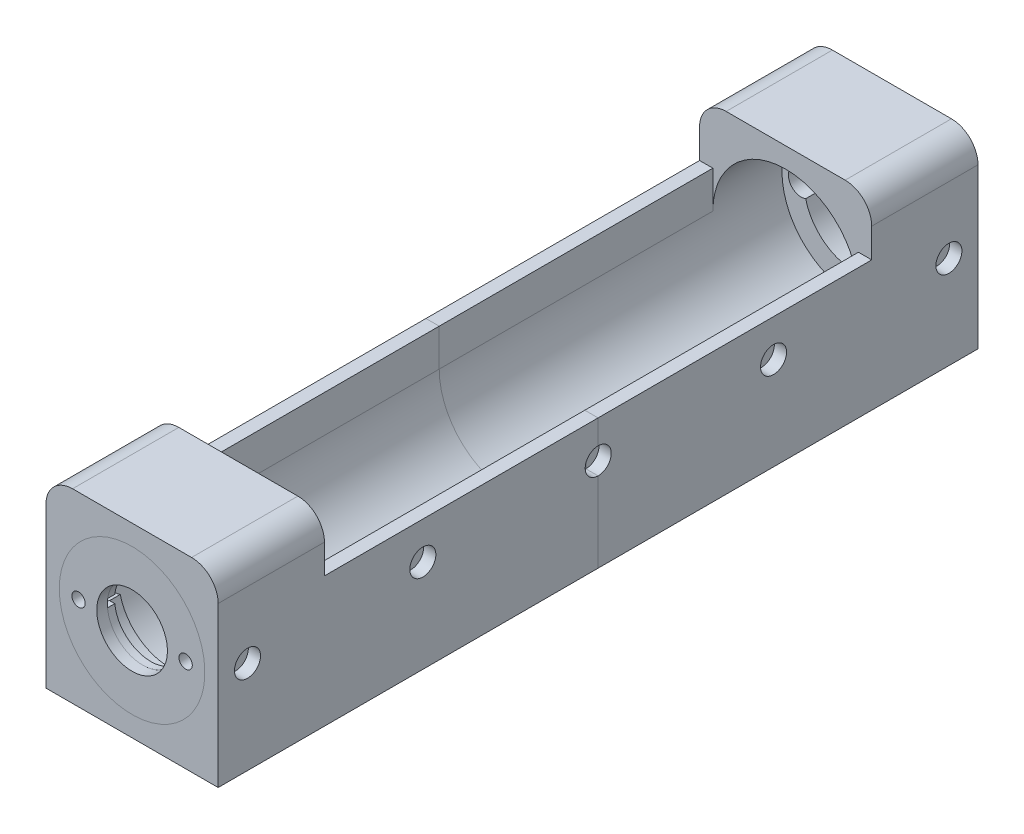
SolidWorks part; units mm, degrees
ref_plane "Alzado" through (0, 0, 0) normal (0, 0, 1) x (1, 0, 0)
ref_plane "Planta" through (0, 0, 0) normal (0, 1, 0) x (1, 0, 0)
ref_plane "Vista lateral" through (0, 0, 0) normal (1, 0, 0) x (0, 0, -1)
sketch "Croquis1" plane through (0, 0, 0) normal (0, 0, 1) x (1, 0, 0)
  line L0 (0, 8.3596) -> (0, -1.3417) construction
  line L1 (9, 0.75) -> (-9, 0.75)
  line L2 (0, 0.75) -> (0, -0.75)
  line L3 (9, -0.75) -> (-9, -0.75)
  line L4 (-9, 0.75) -> (-9, -0.75)
  line L5 (-12.48, 10.7299) -> (-12.48, -4.9079) construction
  line L6 (9, 0.75) -> (9, -0.75)
  line L7 (0, 0) -> (-17.6562, 0) construction
  circle A0 centre (-10.08, 0) radius 2.4
  circle A1 centre (-10.08, 0) radius 0.9
  circle A2 centre (10.08, 0) radius 0.9
  circle A3 centre (10.08, 0) radius 2.4
  circle A4 centre (0, 0) radius 13.7
  point P9 (0, 0)
  dimension "D1" = 1.8
  dimension "D4" = 4.8
  dimension "D6" = 27.4
  dimension "D2" = 1.5
  dimension "D3" = 9
  dimension "D5" = 12.48
extrude "Saliente-Extruir1" add sketch "Croquis1" along normal blind 5 contours A4 L1 A3 L3 A0 region at (-13.3125, 0, 0)
sketch "Croquis2" plane through (0, 0, 5) normal (0, 0, 1) x (1, 0, 0)
  circle A0 centre (0, 0) radius 9.5
  dimension "D1" = 19
extrude "Cortar-Extruir1" cut sketch "Croquis2" against normal blind 3.5
sketch "Croquis3" plane through (0, 0, 1.5) normal (0, 0, 1) x (1, 0, 0)
  circle A0 centre (0, 0) radius 6.8
  dimension "D1" = 13.6
extrude "Cortar-Extruir2" cut sketch "Croquis3" against normal blind 3
sketch "Croquis4" plane through (0, 0, 0) normal (0, 0, -1) x (-1, 0, 0)
  circle A0 centre (0, 0) radius 13.7 construction
  circle A1 centre (0, 0) radius 13.7
  circle A2 centre (0, 0) radius 6.65
  dimension "D1" = 13.3
extrude "Saliente-Extruir2" add sketch "Croquis4" along normal blind 2
sketch "Croquis5" plane through (0, 0, 5) normal (0, 0, 1) x (1, 0, 0)
  circle A0 centre (-10.08, 0) radius 1.25
  circle A1 centre (10.08, 0) radius 1.25
  dimension "D1" = 2.5
  dimension "D2" = 2.5
extrude "Cortar-Extruir3" cut sketch "Croquis5" against normal through all
sketch "Croquis6" plane through (0, 0, -2) normal (0, 0, -1) x (-1, 0, 0)
  line L1 (-16.2, -17.5) -> (16.2, -17.5)
  line L2 (-16.2, -17.5) -> (-16.2, 17.5)
  line L3 (-16.2, 17.5) -> (16.2, 17.5)
  line L4 (16.2, -17.5) -> (16.2, 17.5)
  line L5 (-16.2, -17.5) -> (16.2, 17.5) construction
  line L6 (-16.2, 17.5) -> (16.2, -17.5) construction
  circle A0 centre (0, 0) radius 13.7 construction
  circle A1 centre (0, 0) radius 13.7
  point P0 (0, 0)
  dimension "D1" = 35
  dimension "D2" = 32.4
extrude "Saliente-Extruir3" add sketch "Croquis6" against normal blind 20 separate body
sketch "Croquis8" plane through (0, 0, 18) normal (0, 0, 1) x (1, 0, 0)
  line L0 (-13.7, 0) -> (-13.7, 7)
  line L1 (-13.7, 7) -> (16.2, 7)
  line L2 (13.7, 0) -> (13.7, 7)
  line L3 (13.7, 7) -> (-16.2, 7)
  line L4 (-16.2, 17.5) -> (-16.2, -17.5)
  line L5 (16.2, 17.5) -> (-16.2, 17.5)
  line L6 (16.2, -17.5) -> (16.2, 17.5)
  line L7 (-16.2, -17.5) -> (16.2, -17.5)
  line L8 (-16.2, 17.5) -> (-16.2, 7)
  line L10 (16.2, 7) -> (16.2, 17.5)
  line L11 (-16.2, -17.5) -> (16.2, -17.5)
  line L12 (16.2, 17.5) -> (16.2, -17.5) construction
  line L13 (27.021, 0) -> (-27.7174, 0) construction
  circle A0 centre (0, 0) radius 13.7 construction
  circle A1 centre (0, 0) radius 13.7 construction
  arc A2 (-13.7, 0) -> (13.7, 0) centre (0, 0) ccw
  circle M15 centre (0, 0) radius 13.7
  line M16 (-16.2, 17.5) -> (-16.2, -17.5)
  line M17 (-16.2, -17.5) -> (16.2, -17.5)
  line M18 (16.2, -17.5) -> (16.2, 17.5)
  dimension "D2" = 7
  dimension "D3" = 7
  dimension "D1" = 0
extrude "Saliente-Extruir5" add sketch "Croquis8" along normal blind 51.5 contours L13 M18 M15 M16 M17 | L13 L0 L3 M16 | L13 L1 L2 M18 region at (-14.95, 3.5, 18) region at (0, -14.0682, 18) region at (14.95, 3.5, 18)
ref_plane "Plano1" through (0, 0, 69.5) normal (0, 0, 1) x (1, 0, 0)
mirror "Simetría10" about plane through (0, 0, 69.5) normal (0, 0, 1) of bodies 105 108
sketch "Croquis9" plane through (-16.2, 0, 0) normal (-1, 0, 0) x (0, 0, 1)
  line L0 (0, 0) -> (156.1517, 0) construction
  circle A0 centre (3.4791, 0) radius 2.45
  circle A1 centre (3.4791, 0) radius 16.5 construction
  circle A2 centre (36.4791, 0) radius 16.5 construction
  circle A3 centre (69.4791, 0) radius 16.5 construction
  circle A4 centre (102.4791, 0) radius 16.5 construction
  circle A5 centre (135.4791, 0) radius 16.5 construction
  circle A6 centre (36.4791, 0) radius 2.45
  circle A7 centre (69.4791, 0) radius 2.45
  circle A8 centre (102.4791, 0) radius 2.45
  circle A9 centre (135.4791, 0) radius 2.45
  dimension "D1" = 4.9
  dimension "D3" = 33
  dimension "D2" = 3.4791
extrude "Cortar-Extruir4" cut sketch "Croquis9" against normal blind 2.3
mirror "Simetría11" about plane through (0, 0, 0) normal (1, 0, 0) of "Cortar-Extruir4"
fillet "Redondeo1" radius 5 2 edges at (16.2, 17.5, 8) (-16.2, 17.5, 8)
fillet "Redondeo2" radius 5 2 edges at (16.2, 17.5, 131) (-16.2, 17.5, 131)
ref_plane "Plano2" through (0, -13.7, 0) normal (0, 1, 0) x (1, 0, 0)
sketch "Croquis10" plane through (0, -13.7, 0) normal (0, -1, 0) x (1, 0, 0)
  line L0 (0, -25.2789) -> (0, 143.4615) construction
  circle A0 centre (0, 50) radius 2
  circle A1 centre (0, 113) radius 2
  circle A2 centre (0, 88) radius 2
  circle A3 centre (0, 25) radius 2
  dimension "D1" = 4
  dimension "D2" = 25
  dimension "D3" = 25
  dimension "D4" = 38
  dimension "D5" = 25
